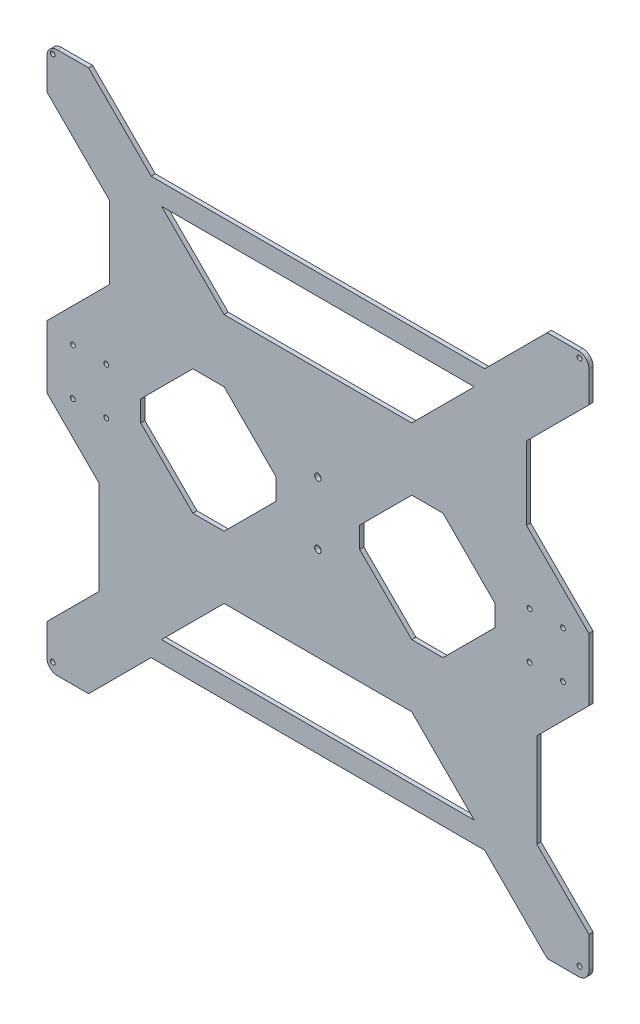
SolidWorks part; units mm, degrees
ref_plane "Front Plane" through (0, 0, 0) normal (0, 0, 1) x (1, 0, 0)
ref_plane "Top Plane" through (0, 0, 0) normal (0, 1, 0) x (1, 0, 0)
ref_plane "Right Plane" through (0, 0, 0) normal (1, 0, 0) x (0, 0, -1)
sketch "Model" plane through (0, 0, 0) normal (0, 0, 1) x (1, 0, 0)
  line L0 (38.5361, 132.6139) -> (38.5361, 132.4727)
  line L1 (38.5361, -178.6774) -> (38.5361, -178.7219)
  line L2 (-253.5639, -197.5861) -> (-253.5639, -197.7273)
  line L3 (-252.5813, 70.3317) -> (-252.5813, 25.8817)
  line L4 (-258.9313, -82.0683) -> (-258.9313, -139.2183)
  line L5 (38.5361, 132.6139) -> (38.5361, 132.4727)
  line L6 (38.5361, -178.6774) -> (38.5361, -178.7219)
  line L7 (7.7687, -139.2183) -> (7.7687, -82.0683)
  line L8 (1.4187, 25.8817) -> (1.4187, 70.3317)
  line L9 (-23.9813, 95.7317) -> (-227.1813, 95.7317)
  line L10 (-290.6813, 108.4317) -> (-252.5813, 70.3317)
  line L11 (-30.3313, -145.5683) -> (-68.4313, -107.4683)
  line L12 (-23.9813, -158.2683) -> (14.1187, -196.3683)
  line L13 (39.5187, 108.4317) -> (39.5187, 127.4817)
  line L14 (-227.1813, 95.7317) -> (-265.2813, 133.8317)
  line L15 (-220.8313, 83.0317) -> (-182.7313, 44.9317)
  line L16 (-274.8413, -45.4288) -> (-254.5213, -45.4288) construction
  line L17 (39.5187, -170.9683) -> (7.7687, -139.2183)
  line L18 (-265.2813, -196.3683) -> (-227.1813, -158.2683)
  line L19 (-182.7313, -107.4683) -> (-68.4313, -107.4683)
  line L20 (-264.6813, -45.4288) -> (-264.6813, -43.5832) construction
  line L21 (1.4187, 70.3317) -> (39.5187, 108.4317)
  line L22 (-23.9813, 95.7317) -> (14.1187, 133.8317)
  line L23 (-30.3313, 83.0317) -> (-68.4313, 44.9317)
  line L25 (-258.9313, -139.2183) -> (-290.6813, -170.9683)
  line L26 (-182.7313, 44.9317) -> (-68.4313, 44.9317)
  line L27 (-220.8313, -145.5683) -> (-182.7313, -107.4683)
  line L28 (-220.8313, -145.5683) -> (-30.3313, -145.5683)
  line L29 (-258.9313, -82.0683) -> (-290.6813, -50.3183)
  line L30 (-290.6813, -12.2183) -> (-290.6813, -50.3183)
  line L31 (-274.8413, -43.9683) -> (-274.8413, -31.2683) construction
  line L32 (-290.6813, -12.2183) -> (-252.5813, 25.8817)
  line L33 (-201.7813, -69.3683) -> (-233.5313, -37.6183)
  line L34 (-182.7313, -69.3683) -> (-201.7813, -69.3683)
  line L35 (1.4187, 25.8817) -> (39.5187, -12.2183)
  line L36 (39.5187, -12.2183) -> (39.5187, -50.3183)
  line L37 (-150.9813, -37.6183) -> (-182.7313, -69.3683)
  line L38 (39.5187, -50.3183) -> (22.4579, -67.3791)
  line L39 (22.4579, -67.3791) -> (7.7687, -82.0683)
  line L40 (-100.1813, -37.6183) -> (-100.1813, -24.9183)
  line L41 (-150.9813, -37.6183) -> (-150.9813, -24.9183)
  line L42 (-150.9813, -24.9183) -> (-182.7313, 6.8317)
  line L43 (-182.7313, 6.8317) -> (-201.7813, 6.8317)
  line L44 (-201.7813, 6.8317) -> (-233.5313, -24.9183)
  line L45 (-233.5313, -24.9183) -> (-233.5313, -37.6183)
  line L46 (-17.6313, -24.9183) -> (-17.6313, -37.6183)
  line L47 (-49.3813, 6.8317) -> (-17.6313, -24.9183)
  line L48 (-220.8313, 83.0317) -> (-30.3313, 83.0317)
  line L49 (-68.4313, 6.8317) -> (-49.3813, 6.8317)
  line L50 (-100.1813, -24.9183) -> (-68.4313, 6.8317)
  line L51 (-100.1813, -37.6183) -> (-68.4313, -69.3683)
  line L52 (-68.4313, -69.3683) -> (-49.3813, -69.3683)
  line L53 (-49.3813, -69.3683) -> (-17.6313, -37.6183)
  line L58 (-265.2813, -196.3683) -> (-284.3313, -196.3683)
  line L59 (-290.6813, -190.0183) -> (-290.6813, -170.9683)
  line L60 (-290.6813, 108.4317) -> (-290.6813, 127.4817)
  line L61 (-284.3313, 133.8317) -> (-265.2813, 133.8317)
  line L62 (14.1187, 133.8317) -> (33.1687, 133.8317)
  line L64 (39.5187, -170.9683) -> (39.5187, -190.0183)
  line L65 (33.1687, -196.3683) -> (14.1187, -196.3683)
  line L71 (-227.1813, -158.2683) -> (-23.9813, -158.2683)
  line L72 (38.5361, -178.6774) -> (38.5361, -178.7219)
  line L74 (-227.1813, -158.2683) -> (-23.9813, -158.2683)
  line L75 (38.5361, -178.6774) -> (38.5361, -178.7219)
  line L77 (-125.5813, 95.7317) -> (-125.5813, -158.2683) construction
  line L78 (-290.6813, -31.2683) -> (39.5187, -31.2683) construction
  arc A0 (33.1687, -196.3683) -> (39.5187, -190.0183) centre (33.1687, -190.0183) ccw
  arc A1 (-290.6813, -190.0183) -> (-284.3313, -196.3683) centre (-284.3313, -190.0183) ccw
  arc A2 (-290.6813, 127.4817) -> (-284.3313, 133.8317) centre (-284.3313, 127.4817) cw
  arc A3 (33.1687, 133.8317) -> (39.5187, 127.4817) centre (33.1687, 127.4817) cw
  circle A4 centre (-287.1253, -190.6025) radius 1.4605
  circle A5 centre (33.7529, -190.6025) radius 1.4605
  circle A6 centre (33.7529, 130.2757) radius 1.4605
  circle A7 centre (-287.1253, 130.2757) radius 1.4605
  circle A8 centre (-274.8413, -45.4288) radius 1.4605
  circle A9 centre (-254.5213, -45.4288) radius 1.4605
  circle A10 centre (23.6787, -45.4288) radius 1.4605
  circle A11 centre (3.3587, -45.4288) radius 1.4605
  circle A12 centre (23.6787, -17.1078) radius 1.4605
  circle A13 centre (3.3587, -17.1078) radius 1.4605
  circle A14 centre (-254.5213, -17.1078) radius 1.4605
  circle A15 centre (-274.8413, -17.1078) radius 1.4605
  circle A16 centre (-125.5813, -12.2183) radius 2
  circle A17 centre (-125.5813, -50.3183) radius 2
  point P72 (-125.5813, -31.2683)
  point P79 (-290.6813, -31.2683)
  point P114 (-125.5813, 83.0317)
  point P116 (39.5187, -31.2683)
  point P120 (-233.5313, -31.2683)
  point P129 (-150.9813, -31.2683)
  point P141 (-290.6813, -180.4933)
  point P149 (-125.5813, 44.9317)
  point P156 (-17.6313, -31.2683)
  dimension "D28" = 6.35
  dimension "D29" = 6.35
  dimension "D30" = 6.35
  dimension "D31" = 6.35
  dimension "D35" = 2.921
  dimension "D36" = 2.921
  dimension "D37" = 2.921
  dimension "D38" = 2.921
  dimension "D53" = 2.921
  dimension "D54" = 2.921
  dimension "D56" = 4
  dimension "D57" = 4
  dimension "D1" = 330.2
  dimension "D2" = 330.2
  dimension "D3" = 135
  dimension "D4" = 135
  dimension "D5" = 38.1
  dimension "D6" = 135
  dimension "D7" = 135
  dimension "D8" = 19.05
  dimension "D9" = 135
  dimension "D10" = 19.05
  dimension "D11" = 31.75
  dimension "D12" = 190.5
  dimension "D13" = 114.3
  dimension "D14" = 38.1
  dimension "D15" = 114.3
  dimension "D16" = 135
  dimension "D17" = 6.35
  dimension "D18" = 38.1
  dimension "D19" = 135
  dimension "D20" = 135
  dimension "D21" = 6.35
  dimension "D22" = 19.05
  dimension "D23" = 25.4
  dimension "D24" = 38.1
  dimension "D25" = 135
  dimension "D26" = 135
  dimension "D27" = 127
  dimension "D32" = 19.05
  dimension "D33" = 19.05
  dimension "D34" = 19.05
  dimension "D39" = 38.1
  dimension "D40" = 19.05
  dimension "D41" = 38.1
  dimension "D42" = 38.1
  dimension "D43" = 135
  dimension "D44" = 19.05
  dimension "D45" = 31.75
  dimension "D46" = 135
  dimension "D47" = 320.8782
  dimension "D48" = 320.8782
  dimension "D49" = 3.556
  dimension "D50" = 3.556
  dimension "D51" = 20.32
  dimension "D52" = 26
  dimension "D55" = 12.7
  dimension "D58" = 38.1
  dimension "D59" = 19.05
extrude "Boss-Extrude1" add sketch "Model" along normal mid plane 2.54 contours A3 L62 L22 L9 L14 L61 A2 L60 L10 L3 L32 L30 L29 L4 L25 L59 A1 L58 L18 L71 L12 L65 A0 L64 L17 L7 L39 L38 L36 L35 L8 L21 L13 A17 A16 A14 A13 A12 A10 A9 region at (-125.5808, -32.1456, 0)
